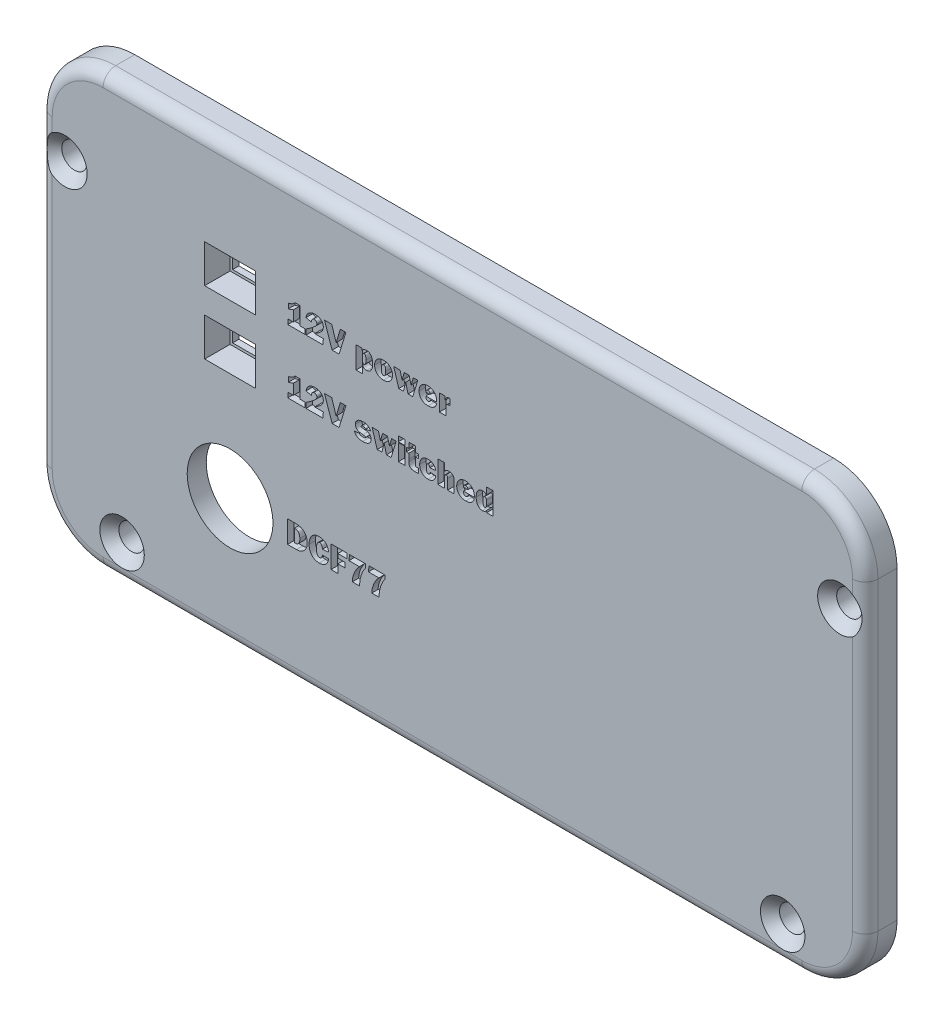
SolidWorks part; units mm, degrees
ref_plane "Front Plane" through (0, 0, 0) normal (0, 0, 1) x (1, 0, 0)
ref_plane "Top Plane" through (0, 0, 0) normal (0, 1, 0) x (1, 0, 0)
ref_plane "Right Plane" through (0, 0, 0) normal (1, 0, 0) x (0, 0, -1)
sketch "Sketch1" plane through (0, 0, 0) normal (0, 0, 1) x (1, 0, 0)
  line L0 (-55, 21) -> (55, -27) construction
  line L1 (-57, -26) -> (57, -26) construction
  line L2 (-57, -26) -> (-57, 26) construction
  line L3 (-57, 26) -> (57, 26) construction
  line L4 (57, -26) -> (57, 26) construction
  line L5 (-57, -26) -> (57, 26) construction
  line L6 (-57, 26) -> (57, -26) construction
  line L7 (-55, -37) -> (55, -37)
  line L8 (-65, -27) -> (-65, 21)
  line L9 (-55, 31) -> (55, 31)
  line L10 (65, -27) -> (65, 21)
  line L11 (55, 21) -> (-55, -27) construction
  line L12 (-62, -27) -> (-62, 21) construction
  line L13 (-55, 28) -> (55, 28) construction
  line L14 (62, -27) -> (62, 21) construction
  line L15 (-55, -34) -> (55, -34) construction
  line L16 (0, 0) -> (0, -3) construction
  line L17 (0, 26) -> (0, 31) construction
  line L18 (-62, -3) -> (-57, -3) construction
  arc A0 (55, 31) -> (65, 21) centre (55, 21) cw
  arc A1 (55, -37) -> (65, -27) centre (55, -27) ccw
  arc A2 (-55, -37) -> (-65, -27) centre (-55, -27) cw
  arc A3 (-65, 21) -> (-55, 31) centre (-55, 21) cw
  arc A4 (-55, -34) -> (-62, -27) centre (-55, -27) cw construction
  arc A5 (-62, 21) -> (-55, 28) centre (-55, 21) cw construction
  arc A6 (55, 28) -> (62, 21) centre (55, 21) cw construction
  arc A7 (55, -34) -> (62, -27) centre (55, -27) ccw construction
  point P0 (0, 0)
  point P6 (0, 0)
  point P37 (62.0711, 20)
  point P38 (0, 0)
  point P39 (62, 20)
  dimension "D3" = 10
  dimension "D1" = 130
  dimension "D2" = 52
  dimension "D4" = 5
  dimension "D5" = 3
  dimension "D6" = 3
extrude "Boss-Extrude1" add sketch "Sketch1" along normal blind 5
sketch "Sketch2" plane through (0, 0, 0) normal (0, 0, -1) x (-1, 0, 0)
  line L1 (55, -37) -> (-55, -37) construction
  line L2 (65, 21) -> (65, -27) construction
  line L3 (-65, -26) -> (65, -26) construction
  line L4 (-65, -27) -> (-65, 21) construction
  circle A0 centre (35, -17) radius 6.75
  circle A1 centre (35, -17) radius 9 construction
  dimension "D1" = 13.5
  dimension "D3" = 18
  dimension "D2" = 30
  dimension "D4" = 11
extrude "Cut-Extrude1" cut sketch "Sketch2" against normal through all
sketch "Sketch3" plane through (0, 0, 0) normal (0, 0, -1) x (-1, 0, 0)
  line L0 (-39.5, 19) -> (20.5, 19) construction
  circle A0 centre (-39.5, 19) radius 1.8
  circle A1 centre (20.5, 19) radius 1.8
  circle A2 centre (-43.43, -14.1) radius 1.8
  circle A3 centre (9.5, -15) radius 1.8
  point P5 (-9.5, 19)
  dimension "D2" = 3.6
  dimension "D1" = 60
  dimension "D3" = 19
  dimension "D4" = 9.5
  dimension "D5" = 33.1
  dimension "D6" = 3.93
  dimension "D7" = 34
  dimension "D8" = 11
extrude "Cut-Extrude2" cut sketch "Sketch3" against normal offset from surface (3 mm away) 2 up to face at (-41.75, -17, 5)
sketch "Sketch6" plane through (0, 0, 0) normal (0, 0, -1) x (-1, 0, 0)
  circle A0 centre (35, -17) radius 11
  dimension "D1" = 22
extrude "Cut-Extrude4" cut sketch "Sketch6" against normal offset from surface (2 mm away) 3 up to face at (-41.75, -17, 5)
sketch "Sketch7" plane through (0, 0, 5) normal (0, 0, 1) x (1, 0, 0)
  line L0 (-35, 13) -> (-35, 3) construction
  line L1 (-39, 0) -> (-31, 0)
  line L2 (-39, 0) -> (-39, 6)
  line L3 (-39, 6) -> (-31, 6)
  line L4 (-31, 0) -> (-31, 6)
  line L5 (-39, 0) -> (-31, 6) construction
  line L6 (-39, 6) -> (-31, 0) construction
  line L7 (-39, 10) -> (-31, 10)
  line L8 (-39, 10) -> (-39, 16)
  line L9 (-39, 16) -> (-31, 16)
  line L10 (-31, 10) -> (-31, 16)
  line L11 (-39, 10) -> (-31, 16) construction
  line L12 (-39, 16) -> (-31, 10) construction
  line L13 (-35, 3) -> (-35, -17) construction
  point P0 (-35, 3)
  point P5 (-35, 13)
  dimension "D1" = 8
  dimension "D2" = 6
  dimension "D3" = 20
  dimension "D4" = 10
extrude "Cut-Extrude5" cut sketch "Sketch7" against normal through all
sketch "Sketch8" plane through (0, 0, 5) normal (0, 0, 1) x (1, 0, 0)
  line L0 (-26.25, 11.25) -> (65, 11.25) construction
  line L2 (-26.25, 1.25) -> (65, 1.25) construction
  line L4 (-26.25, -18.75) -> (65, -18.75) construction
  line L5 (-31, 10) -> (-31, 16) construction
  line L7 (-31, 13) -> (-31, 11.25) construction
  line L8 (-31, 3) -> (-31, 1.25) construction
  line L9 (65, -27) -> (65, 21) construction
  line L10 (-28.25, -17) -> (-28.25, -18.75) construction
  line L11 (-28.25, -17) -> (-35, -17) construction
  line L12 (-31, 11.25) -> (-26.25, 11.25) construction
  line L13 (-31, 0) -> (-31, 6) construction
  line L14 (-31, 1.25) -> (-26.25, 1.25) construction
  line L15 (-26.25, -18.75) -> (-28.25, -18.75) construction
  line L16 (-26.25, 11.25) -> (-26.25, 1.25) construction
  line L17 (-26.25, 1.25) -> (-26.25, -18.75) construction
  circle A0 centre (-35, -17) radius 6.75 construction
  text T0 "12V power" font "Franklin Gothic Heavy" height 3.5
  text T1 "12V switched" font "Franklin Gothic Heavy" height 3.5
  text T2 "DCF77" font "Franklin Gothic Heavy" height 3.5
  dimension "D1" = 1.75
  dimension "D2" = 2
extrude "Cut-Extrude6" cut sketch "Sketch8" against normal blind 1
sketch "Sketch9" plane through (0, 0, 0) normal (0, 0, -1) x (-1, 0, 0)
  line L0 (39, 6) -> (39, 0) construction
  line L1 (39, 0) -> (31, 0) construction
  line L2 (31, 0) -> (31, 6) construction
  line L3 (31, 6) -> (39, 6) construction
  line L4 (31, 16) -> (39, 16) construction
  line L5 (39, 16) -> (39, 10) construction
  line L6 (39, 10) -> (31, 10) construction
  line L7 (31, 10) -> (31, 16) construction
  line L8 (39, 6) -> (39, 0)
  line L9 (39, 0) -> (31, 0)
  line L10 (31, 0) -> (31, 6)
  line L11 (31, 6) -> (39, 6)
  line L12 (31, 16) -> (39, 16)
  line L13 (39, 16) -> (39, 10)
  line L14 (39, 10) -> (31, 10)
  line L15 (31, 10) -> (31, 16)
  line L16 (31.4, 15.6) -> (38.6, 15.6)
  line L17 (38.6, 15.6) -> (38.6, 10.4)
  line L18 (38.6, 10.4) -> (31.4, 10.4)
  line L19 (31.4, 10.4) -> (31.4, 15.6)
  line L20 (38.6, 5.6) -> (38.6, 0.4)
  line L21 (38.6, 0.4) -> (31.4, 0.4)
  line L22 (31.4, 0.4) -> (31.4, 5.6)
  line L23 (31.4, 5.6) -> (38.6, 5.6)
  line L24 (35, 15.6) -> (35, 16) construction
  line L25 (35, 5.6) -> (35, 6) construction
  dimension "D1" = 0.4
extrude "Boss-Extrude2" add sketch "Sketch9" against normal blind 1
sketch "Sketch10" plane through (0, 0, 0) normal (0, 0, -1) x (-1, 0, 0)
  circle A8 centre (-39.5, 19) radius 4
  circle A9 centre (20.5, 19) radius 4
  circle A10 centre (9.5, -15) radius 4
  circle A11 centre (-43.43, -14.1) radius 4
  point P1 (-43.43, -14.1)
  point P3 (9.5, -15)
  point P5 (12.3935, 17.6404)
  point P7 (-39.5, 19)
  point P8 (20.5, 19)
  dimension "D1" = 8
extrude "Boss-Extrude3" add sketch "Sketch10" along normal blind 5
sketch "Sketch11" plane through (0, 0, 0) normal (0, 0, -1) x (-1, 0, 0)
  line L0 (55, -37) -> (-55, -37) construction
  line L1 (-45.55, 4.71) -> (-35.55, 4.71)
  line L2 (-45.55, 4.71) -> (-45.55, -5.29)
  line L3 (-45.55, -5.29) -> (-35.55, -5.29)
  line L4 (-35.55, 4.71) -> (-35.55, -5.29)
  line L5 (-45.55, 4.71) -> (-35.55, -5.29) construction
  line L6 (-45.55, -5.29) -> (-35.55, 4.71) construction
  line L7 (-65, -27) -> (-65, 21) construction
  point P0 (-40.55, -0.29)
  dimension "D1" = 36.71
  dimension "D2" = 10
  dimension "D3" = 24.45
extrude "Cut-Extrude7" cut sketch "Sketch11" against normal blind 3
fillet "Fillet1" radius 1 8 edges at (40.55, -5.29, 3) (45.55, -0.29, 3) (40.55, 4.71, 3) (35.55, -0.29, 3) (45.55, -5.29, 1.5) (35.55, -5.29, 1.5) (35.55, 4.71, 1.5) (45.55, 4.71, 1.5)
sketch "Sketch12" plane through (0, 0, 5) normal (0, 0, 1) x (1, 0, 0)
  line L0 (-61, -31.5) -> (-52, -31.5) construction
  line L5 (0, 16) -> (0, -31.5) construction
  line L6 (-61, 16) -> (61, 16) construction
  line L7 (-61, 16) -> (-61, -31.5) construction
  line L8 (-61, -31.5) -> (61, -31.5) construction
  line L9 (61, 16) -> (61, -31.5) construction
  line L10 (55, 31) -> (-55, 31) construction
  line L11 (-55, -37) -> (55, -37) construction
  line L12 (-65, 21) -> (-65, -27) construction
  line L13 (52, -31.5) -> (61, -31.5) construction
  circle A0 centre (-61, 16) radius 2
  circle A1 centre (61, 16) radius 2
  circle A2 centre (52, -31.5) radius 2
  circle A3 centre (-52, -31.5) radius 2
  dimension "D4" = 4
  dimension "D1" = 15
  dimension "D2" = 5.5
  dimension "D3" = 4
  dimension "D5" = 9
extrude "Cut-Extrude8" cut sketch "Sketch12" against normal through all
sketch "Sketch13" plane through (0, 0, -5) normal (0, 0, -1) x (-1, 0, 0)
  circle A0 centre (-39.5, 19) radius 2.1
  circle A1 centre (20.5, 19) radius 2.1
  circle A2 centre (9.5, -15) radius 2.1
  circle A3 centre (-43.43, -14.1) radius 2.1
  dimension "D1" = 4.2
extrude "Cut-Extrude9" cut sketch "Sketch13" against normal blind 3
sketch "Sketch14" plane through (0, 0, -5) normal (0, 0, -1) x (-1, 0, 0)
  circle A0 centre (-39.5, 19) radius 1.8
  circle A1 centre (20.5, 19) radius 1.8
  circle A2 centre (9.5, -15) radius 1.8
  circle A3 centre (-43.43, -14.1) radius 1.8
  dimension "D1" = 3.6
extrude "Cut-Extrude10" cut sketch "Sketch14" against normal offset from surface (7 mm away) 3 up to face at (-59, 16, 5)
fillet "Fillet3" radius 2 4 edges at (39.43, -14.1, 0) (-13.5, -15, 0) (-24.5, 19, 0) (35.5, 19, 0)
chamfer "Chamfer1" distance 1.5 angle 45 4 edges at (-59, 16, 5) (63, 16, 5) (54, -31.5, 5) (-50, -31.5, 5)
fillet "Fillet2" radius 2 8 edges at (62.0711, 28.0711, 5) (65, -3, 5) (62.0711, -34.0711, 5) (0, -37, 5) (-62.0711, -34.0711, 5) (-65, -3, 5) (-62.0711, 28.0711, 5) (0, 31, 5)
